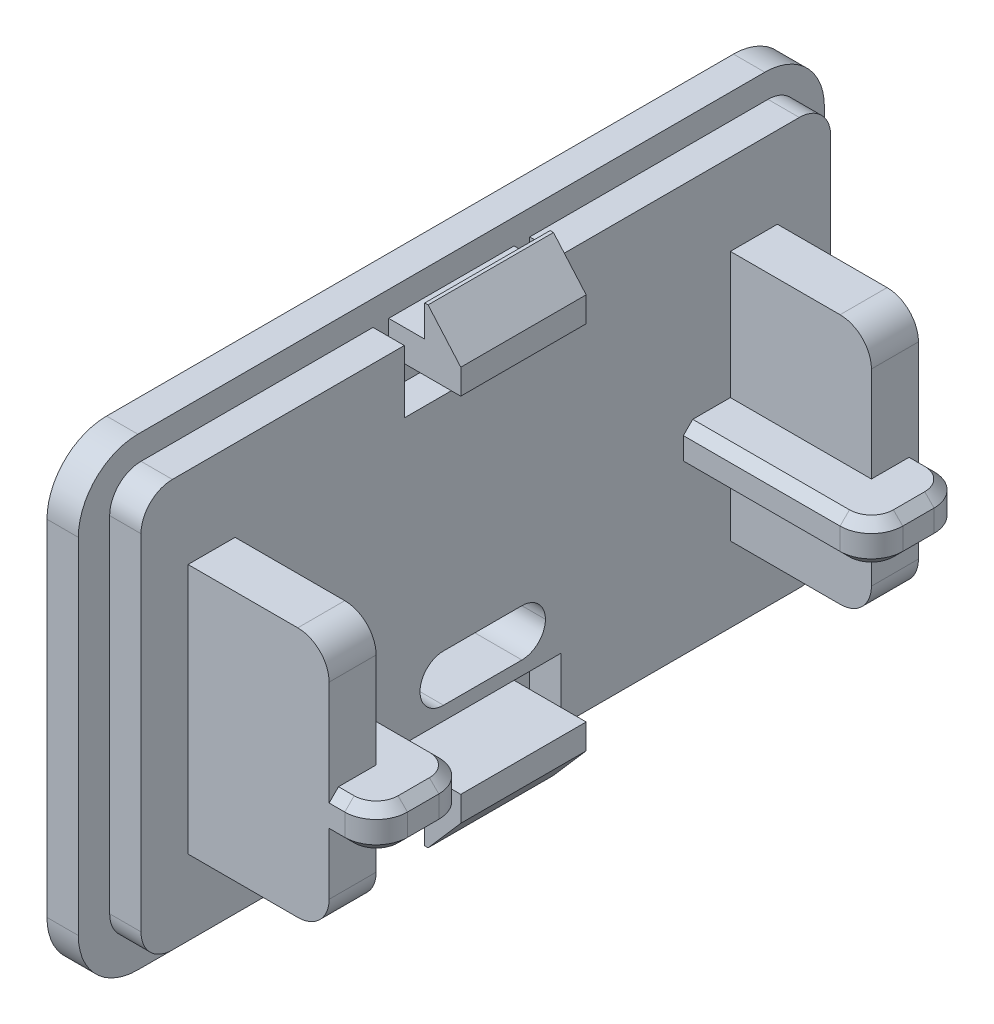
SolidWorks part; units mm, degrees
ref_plane "前视基准面" through (0, 0, 0) normal (0, 0, 1) x (1, 0, 0)
ref_plane "上视基准面" through (0, 0, 0) normal (0, 1, 0) x (1, 0, 0)
ref_plane "右视基准面" through (0, 0, 0) normal (1, 0, 0) x (0, 0, -1)
sketch "草图1" plane through (0, 0, 0) normal (1, 0, 0) x (0, 0, -1)
  line L4 (-8.6202, -6.7104) -> (-8.6202, 4.2896)
  line L5 (12.3798, -7.7104) -> (-7.6202, -7.7104)
  line L6 (13.3798, 4.2896) -> (13.3798, -6.7104)
  line L7 (-7.6202, 5.2896) -> (12.3798, 5.2896)
  arc A4 (-7.6202, 5.2896) -> (-8.6202, 4.2896) centre (-7.6202, 4.2896) ccw
  arc A5 (-8.6202, -6.7104) -> (-7.6202, -7.7104) centre (-7.6202, -6.7104) ccw
  arc A6 (12.3798, -7.7104) -> (13.3798, -6.7104) centre (12.3798, -6.7104) ccw
  arc A7 (13.3798, 4.2896) -> (12.3798, 5.2896) centre (12.3798, 4.2896) ccw
extrude "凸台-拉伸1" add sketch "草图1" along normal blind 1
sketch "草图2" plane through (0, 0, 0) normal (-1, 0, 0) x (0, 0, 1)
  line L12 (9.6202, -6.8104) -> (9.6202, 4.1896)
  line L13 (-12.2798, -8.7104) -> (7.7202, -8.7104)
  line L14 (-14.1798, 4.1896) -> (-14.1798, -6.8104)
  line L15 (7.7202, 6.0896) -> (-12.2798, 6.0896)
  arc A12 (9.6202, 4.1896) -> (7.7202, 6.0896) centre (7.7202, 4.1896) ccw
  arc A13 (7.7202, -8.7104) -> (9.6202, -6.8104) centre (7.7202, -6.8104) ccw
  arc A14 (-14.1798, -6.8104) -> (-12.2798, -8.7104) centre (-12.2798, -6.8104) ccw
  arc A15 (-12.2798, 6.0896) -> (-14.1798, 4.1896) centre (-12.2798, 4.1896) ccw
extrude "凸台-拉伸2" add sketch "草图2" along normal blind 1
sketch "草图3" plane through (1, 0, 0) normal (1, 0, 0) x (0, 0, -1)
  line L0 (14.1798, 4.1896) -> (14.1798, -6.8104) construction
  line L1 (-7.1202, 2.6896) -> (-5.6202, 2.6896)
  line L2 (-7.1202, 2.6896) -> (-7.1202, -5.3104)
  line L3 (-7.1202, -5.3104) -> (-5.6202, -5.3104)
  line L4 (-5.6202, 2.6896) -> (-5.6202, -5.3104)
  line L5 (10.1798, 2.6896) -> (11.6798, 2.6896)
  line L6 (10.1798, 2.6896) -> (10.1798, -5.3104)
  line L7 (10.1798, -5.3104) -> (11.6798, -5.3104)
  line L8 (11.6798, 2.6896) -> (11.6798, -5.3104)
  line L9 (-9.6202, -6.8104) -> (-9.6202, 4.1896) construction
  point P11 (14.1798, -1.3104)
  point P12 (11.6798, -1.3104)
  point P13 (-5.6202, -1.3104)
  dimension "D1" = 1.5
  dimension "D2" = 1.5
  dimension "D3" = 8
  dimension "D4" = 8
  dimension "D5" = 2.5
  dimension "D6" = 2.5
extrude "凸台-拉伸3" add sketch "草图3" along normal blind 4.5
sketch "草图4" plane through (1, 0, 0) normal (1, 0, 0) x (0, 0, -1)
  line L0 (14.1798, 4.1896) -> (14.1798, -6.8104) construction
  line L1 (-7.1202, -1.3496) -> (-4.1202, -1.3496)
  line L2 (-7.1202, -1.3496) -> (-7.1202, -2.6496)
  line L3 (-7.1202, -2.6496) -> (-4.1202, -2.6496)
  line L4 (-4.1202, -1.3496) -> (-4.1202, -2.6496)
  line L5 (8.6798, -1.3496) -> (11.6798, -1.3496)
  line L6 (8.6798, -1.3496) -> (8.6798, -2.6496)
  line L7 (8.6798, -2.6496) -> (11.6798, -2.6496)
  line L8 (11.6798, -1.3496) -> (11.6798, -2.6496)
  line L9 (-9.6202, -6.8104) -> (-9.6202, 4.1896) construction
  dimension "D1" = 2.5
  dimension "D2" = 3
  dimension "D3" = 2.5
  dimension "D4" = 3
  dimension "D5" = 1.3
  dimension "D6" = 1.3
extrude "凸台-拉伸4" add sketch "草图4" along normal blind 6
fillet "圆角1" radius 1 8 edges at (5.5, -5.3104, 6.3702) (5.5, -5.3104, -10.9298) (5.5, 2.6896, -10.9298) (5.5, 2.6896, 6.3702) (7, -1.9996, -8.6798) (7, -1.9996, -11.6798) (7, -1.9996, 7.1202) (7, -1.9996, 4.1202)
chamfer "倒角1" distance 0.3 angle 45 20 edges at (3.5, -2.6496, -8.6798) (5.75, -2.6496, -11.6798) (6.7071, -2.6496, -8.9727) (6.7071, -2.6496, -11.3869) (7, -2.6496, -10.1798) (5.75, -1.3496, -11.6798) (3.5, -1.3496, -8.6798) (6.7071, -1.3496, -11.3869) (6.7071, -1.3496, -8.9727) (7, -1.3496, -10.1798) (5.75, -2.6496, 7.1202) (3.5, -2.6496, 4.1202) (6.7071, -2.6496, 6.8273) (6.7071, -2.6496, 4.4131) (7, -2.6496, 5.6202) (3.5, -1.3496, 4.1202) (5.75, -1.3496, 7.1202) (6.7071, -1.3496, 4.4131) (6.7071, -1.3496, 6.8273) (7, -1.3496, 5.6202)
sketch "草图5" plane through (1, 0, 0) normal (1, 0, 0) x (0, 0, -1)
  line L5 (12.2798, -8.7104) -> (-7.7202, -8.7104) construction
  line L10 (-0.2202, -5.7104) -> (4.7798, -5.7104)
  line L11 (-0.2202, -5.7104) -> (-0.2202, -7.7104)
  line L12 (-0.2202, -7.7104) -> (4.7798, -7.7104)
  line L13 (4.7798, -5.7104) -> (4.7798, -7.7104)
  line L14 (-0.2202, -5.7104) -> (4.7798, -7.7104) construction
  line L15 (-0.2202, -7.7104) -> (4.7798, -5.7104) construction
  line L16 (-7.6202, -7.7104) -> (12.3798, -7.7104) construction
  line L17 (12.3798, 5.2896) -> (-7.6202, 5.2896) construction
  line L18 (-0.2202, 5.2896) -> (4.7798, 5.2896)
  line L19 (-0.2202, 5.2896) -> (-0.2202, 3.2896)
  line L20 (-0.2202, 3.2896) -> (4.7798, 3.2896)
  line L21 (4.7798, 5.2896) -> (4.7798, 3.2896)
  line L22 (-0.2202, 5.2896) -> (4.7798, 3.2896) construction
  line L23 (-0.2202, 3.2896) -> (4.7798, 5.2896) construction
  point P0 (2.2798, 4.2896)
  point P7 (0, 0)
  point P20 (2.2798, -6.7104)
  point P26 (2.2798, -8.7104)
  dimension "D1" = 5
  dimension "D2" = 2
  dimension "D3" = 2
  dimension "D4" = 5
extrude "切除-拉伸1" cut sketch "草图5" against normal blind 1
sketch "草图6" plane through (0, 0, 0) normal (1, 0, 0) x (0, 0, -1)
  line L0 (4.7798, -5.7104) -> (-0.2202, -5.7104) construction
  line L1 (0.2798, -6.7104) -> (4.2798, -6.7104)
  line L2 (0.2798, -6.7104) -> (0.2798, -7.7104)
  line L3 (0.2798, -7.7104) -> (4.2798, -7.7104)
  line L4 (4.2798, -6.7104) -> (4.2798, -7.7104)
  line L5 (0.2798, -6.7104) -> (4.2798, -7.7104) construction
  line L6 (0.2798, -7.7104) -> (4.2798, -6.7104) construction
  line L11 (-0.2202, 5.2896) -> (-7.6202, 5.2896) construction
  line L12 (0.2798, 5.2896) -> (4.2798, 5.2896)
  line L17 (0.2798, 5.2896) -> (0.2798, 4.2896)
  line L18 (0.2798, 4.2896) -> (4.2798, 4.2896)
  line L21 (4.2798, 5.2896) -> (4.2798, 4.2896)
  line L22 (0.2798, 5.2896) -> (4.2798, 4.2896) construction
  line L23 (0.2798, 4.2896) -> (4.2798, 5.2896) construction
  point P0 (2.2798, -7.2104)
  point P5 (2.2798, 4.7896)
  point P6 (0, 0)
  point P13 (0, 0)
  point P14 (0, 0)
  point P26 (2.2798, -5.7104)
  dimension "D1" = 4
  dimension "D2" = 1
  dimension "D3" = 4
  dimension "D5" = 1
extrude "凸台-拉伸5" add sketch "草图6" along normal blind 2.3
sketch "草图7" plane through (0, -7.7104, 0) normal (0, -1, 0) x (1, 0, 0)
  line L0 (2.3, -0.2798) -> (0, -0.2798) construction
  line L1 (2.3, -0.2798) -> (1.15, -0.2798)
  line L2 (2.3, -0.2798) -> (2.3, -4.2798)
  line L3 (2.3, -4.2798) -> (1.15, -4.2798)
  line L4 (1.15, -0.2798) -> (1.15, -4.2798)
  line L5 (2.3, -0.2798) -> (2.3, -4.2798) construction
  line L6 (2.3, -4.2798) -> (0, -4.2798) construction
extrude "凸台-拉伸6" add sketch "草图7" along normal blind 1
sketch "草图10" plane through (-1, 0, 0) normal (-1, 0, 0) x (0, 0, 1)
  line L0 (7.7202, 6.0896) -> (-12.2798, 6.0896) construction
  line L1 (-4.2798, -3.7738) -> (-0.2798, -3.7738)
  line L2 (-4.2798, -3.7738) -> (-4.2798, -5.2738)
  line L3 (-4.2798, -5.2738) -> (-0.2798, -5.2738)
  line L4 (-0.2798, -3.7738) -> (-0.2798, -5.2738)
  line L5 (-12.2798, -8.7104) -> (7.7202, -8.7104) construction
  point P6 (-2.2798, -5.2738)
  point P9 (-2.2798, -8.7104)
  dimension "D1" = 4
  dimension "D2" = 1.5
  dimension "D3" = 9.8634
extrude "切除-拉伸2" cut sketch "草图10" against normal up to next
fillet "圆角2" radius 0.75 4 edges at (0, -5.2738, -0.2798) (0, -3.7738, -0.2798) (0, -3.7738, -4.2798) (0, -5.2738, -4.2798)
sketch "草图11" plane through (0, 5.2896, 0) normal (0, 1, 0) x (1, 0, 0)
  line L4 (2.3, 0.2798) -> (2.3, 4.2798)
  line L5 (1.15, 0.2798) -> (2.3, 0.2798)
  line L6 (1.15, 4.2798) -> (1.15, 0.2798)
  line L7 (2.3, 4.2798) -> (1.15, 4.2798)
  line L8 (2.3, 0.2798) -> (2.3, 4.2798)
  line L9 (1.15, 0.2798) -> (2.3, 0.2798)
  line L10 (1.15, 4.2798) -> (1.15, 0.2798)
  line L11 (2.3, 4.2798) -> (1.15, 4.2798)
  dimension "D1" = 0
extrude "凸台-拉伸7" add sketch "草图11" along normal blind 1
chamfer "倒角2" distance 1.2 angle 41 2 edges at (2.3, -8.7104, -2.2798) (2.3, 6.2896, -2.2798) first distance on face at (2.3, -7.7104, -2.2798) first distance on face at (2.3, 5.2896, -2.2798)
